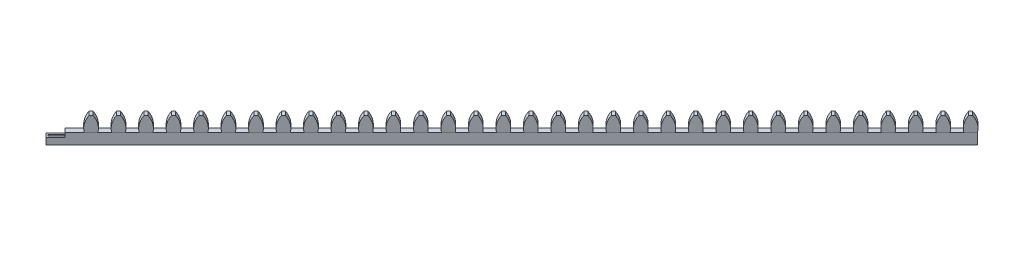
SolidWorks part; units mm, degrees
ref_plane "Front Plane" through (0, 0, 0) normal (0, 0, 1) x (1, 0, 0)
ref_plane "Top Plane" through (0, 0, 0) normal (0, 1, 0) x (1, 0, 0)
ref_plane "Right Plane" through (0, 0, 0) normal (1, 0, 0) x (0, 0, -1)
sketch "Sketch1" plane through (0, 0, 0) normal (0, 1, 0) x (1, 0, 0)
  line L0 (0, 0) -> (215.6676, 215.6676)
  line L5 (0, 0) -> (-1.7678, 1.7678)
  line L6 (-1.7678, 1.7678) -> (213.8998, 217.4353)
  line L7 (215.6676, 215.6676) -> (213.8998, 217.4353)
  dimension "D1" = 2.5
  dimension "D2" = 305
  dimension "D3" = 45
extrude "Boss-Extrude1" add sketch "Sketch1" along normal blind 5
sketch "Sketch3" plane through (-1.7678, 0, -1.7678) normal (-0.7071, 0, -0.7071) x (-0.7071, 0, 0.7071)
  line L0 (-305, 5) -> (0, 5) construction
  line L1 (-300.5, 5) -> (-305, 5)
  arc A0 (-302.115, 11.79) -> (-303.385, 11.79) centre (-302.75, -12.2016) ccw
  arc A1 (-300.5, 5) -> (-302.115, 11.79) centre (-308.7409, 6.627) ccw
  arc A2 (-303.385, 11.79) -> (-305, 5) centre (-296.7591, 6.627) ccw
  point P8 (-302.75, 5)
  point P9 (-302.75, 11.7984)
  dimension "D2" = 8.4
  dimension "D1" = 1.27
  dimension "D4" = 6.79
  dimension "D5" = 24
  dimension "D6" = 8.4
  dimension "D3" = 4.5
extrude "Boss-Extrude2" add sketch "Sketch3" against normal blind 2.5 separate body
pattern_linear "LPattern1" count 33 spacing 9 along (-0.7071, 0, 0.7071) of "Boss-Extrude2"
sketch "Sketch4" plane through (0, 5, 0) normal (0, 1, 0) x (1, 0, 0)
  line L0 (-1.2728, 2.2627) -> (0.495, 0.495)
  line L1 (213.8998, 217.4353) -> (-1.7678, 1.7678) construction
  line L2 (0, 0) -> (215.6676, 215.6676) construction
  line L3 (-1.7678, 1.7678) -> (0, 0) construction
  line L4 (-0.7778, 1.7678) -> (3.1113, 5.6569)
  line L5 (0, 0.9899) -> (3.8891, 4.879)
  line L6 (3.1113, 5.6569) -> (3.4648, 6.0104)
  line L7 (-1.2728, 2.2627) -> (2.6163, 6.1518)
  line L8 (3.1113, 5.6569) -> (2.6163, 6.1518)
  line L9 (0.495, 0.495) -> (4.3841, 4.3841)
  line L10 (4.3841, 4.3841) -> (3.8891, 4.879)
  line L11 (-1.2728, 2.2627) -> (-1.7678, 1.7678)
  line L12 (-1.7678, 1.7678) -> (0, 0)
  line L13 (0, 0) -> (0.495, 0.495)
  line L14 (2.9698, 6.5054) -> (4.7376, 4.7376)
  line L15 (3.8891, 4.879) -> (4.2426, 5.2326)
  line L16 (4.7376, 4.7376) -> (4.3841, 4.3841)
  line L17 (2.9698, 6.5054) -> (2.6163, 6.1518)
  line L18 (3.1113, 5.6569) -> (3.8891, 4.879)
  line M5 (-1.7678, 1.7678) -> (0, 0)
  line M6 (0, 0) -> (215.6676, 215.6676)
  line M8 (213.8998, 217.4353) -> (-1.7678, 1.7678)
  dimension "D1" = 0.7
  dimension "D2" = 0.7
  dimension "D3" = 0.7
  dimension "D4" = 5.5
  dimension "D6" = 90
extrude "Cut-Extrude1" cut sketch "Sketch4" against normal blind 6.5 contours L5 L4 L0 region at (1.5556, 5, -3.3234)
extrude "Cut-Extrude2" cut sketch "Sketch4<4>" against normal blind 2 contours L10 L5 L0 M6 | L0 M8 M5 M6 | L4 L8 L0 M8 region at (0.9192, 5, -3.9598) region at (-0.6364, 5, -1.1314) region at (2.192, 5, -2.687)
sketch "Sketch4<4>" plane through (0, 5, 0) normal (0, 1, 0) x (1, 0, 0) same geometry as "Sketch4"
